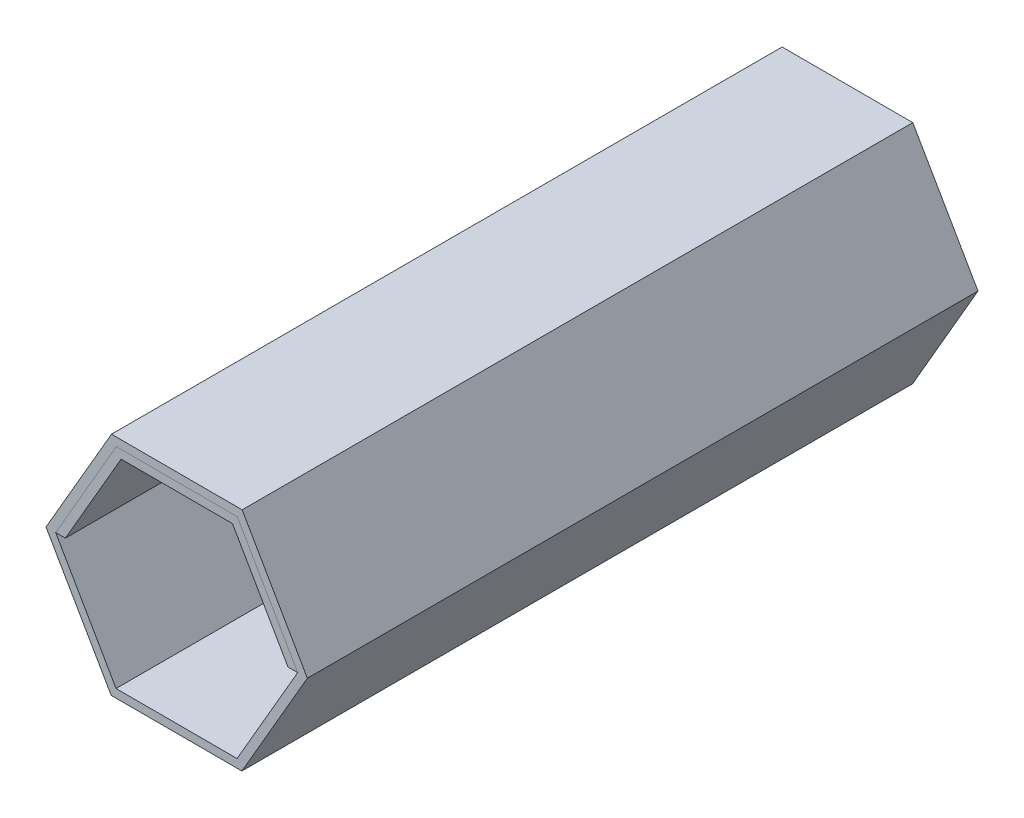
SolidWorks part; units mm, degrees
ref_plane "Front Plane" through (0, 0, 0) normal (0, 0, 1) x (1, 0, 0)
ref_plane "Top Plane" through (0, 0, 0) normal (0, 1, 0) x (1, 0, 0)
ref_plane "Right Plane" through (0, 0, 0) normal (1, 0, 0) x (0, 0, -1)
sketch "Sketch1" plane through (0, 0, 0) normal (0, 0, 1) x (1, 0, 0)
  line L0 (7.2318, 12.4914) -> (-7.2019, 12.5086)
  line L1 (7.8104, 13.4907) -> (-7.7781, 13.5093)
  line L2 (-7.7781, 13.5093) -> (-15.5884, 0.0187)
  line L3 (-15.5884, 0.0187) -> (-7.8104, -13.4907)
  line L4 (-7.8104, -13.4907) -> (7.7781, -13.5093)
  line L5 (7.7781, -13.5093) -> (15.5884, -0.0187)
  line L6 (15.5884, -0.0187) -> (7.8104, 13.4907)
  line L7 (-7.2019, 12.5086) -> (-14.4337, 0.0173)
  line L8 (-14.4337, 0.0173) -> (-7.2318, -12.4914)
  line L9 (-7.2318, -12.4914) -> (7.2019, -12.5086)
  line L10 (7.2019, -12.5086) -> (14.4337, -0.0173)
  line L11 (14.4337, -0.0173) -> (7.2318, 12.4914)
  line L12 (-8.0673, 13.0097) -> (-15.2992, 0.5183)
  line L13 (15.3004, 0.4817) -> (8.0985, 12.9903)
  line L14 (13.5671, -0.5162) -> (6.6533, 11.492)
  line L15 (6.6533, 11.492) -> (-6.6258, 11.5079)
  line L16 (-6.6258, 11.5079) -> (-13.5683, -0.4838)
  line L17 (-13.2882, 0) -> (-13.5, 0.0032)
  line L18 (55, 0) -> (-55, 0) construction
  line L19 (14.4337, -0.0173) -> (13.2798, -0.0173)
  line L20 (-14.4337, 0.0173) -> (-13.2782, 0.0173)
  circle A0 centre (0, 0) radius 13.5 construction
  dimension "D1" = 27
  dimension "D2" = 1
  dimension "D3" = 1
  dimension "D4" = 1
extrude "Boss-Extrude1" add sketch "Sketch1" along normal blind 80 contours L5 L6 L1 L2 L3 L4 L11 L10 L9 L8 L7 L0 region at (7.5969, 13.0346, 0)
extrude "Boss-Extrude2" add sketch "Sketch1<3>" along normal blind 80 separate body contours L7 L20 L16 L15 L14 L19 L11 L0 region at (10.5601, 6.08, 0)
sketch "Sketch1<3>" plane through (0, 0, 0) normal (0, 0, 1) x (1, 0, 0) same geometry as "Sketch1"
